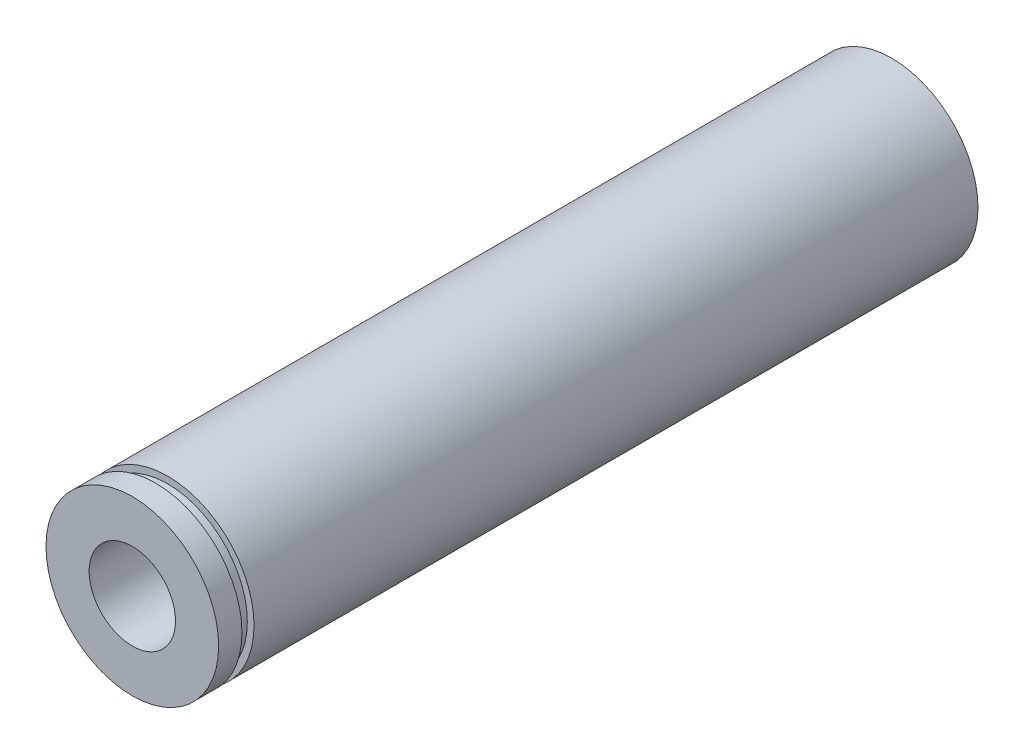
SolidWorks part; units mm, degrees
ref_plane "Front Plane" through (0, 0, 0) normal (0, 0, 1) x (1, 0, 0)
ref_plane "Top Plane" through (0, 0, 0) normal (0, 1, 0) x (1, 0, 0)
ref_plane "Right Plane" through (0, 0, 0) normal (1, 0, 0) x (0, 0, -1)
sketch "Sketch1" plane through (0, 0, 0) normal (0, 0, 1) x (1, 0, 0)
  circle A0 centre (0, 0) radius 6.35
  circle A1 centre (0, 0) radius 3.175
  dimension "D1" = 12.7
  dimension "D2" = 6.35
extrude "Boss-Extrude1" add sketch "Sketch1" along normal mid plane 55.8546
sketch "Sketch2" plane through (0, 0, 0) normal (1, 0, 0) x (0, 0, -1)
  line L0 (-2.4056, 0) -> (1.6345, 0) construction
  line L1 (-26.2128, 6.858) -> (-25.3238, 6.858)
  line L2 (-26.2128, 6.858) -> (-26.2128, 5.8547)
  line L3 (-26.2128, 5.8547) -> (-25.3238, 5.8547)
  line L4 (-25.3238, 6.858) -> (-25.3238, 5.8547)
  line L5 (-27.9273, 6.35) -> (-27.9273, -6.35) construction
  dimension "D1" = 0.889
  dimension "D2" = 5.8547
  dimension "D3" = 1.7145
revolve "Cut-Revolve1" cut sketch "Sketch2" angle 360 about L0
